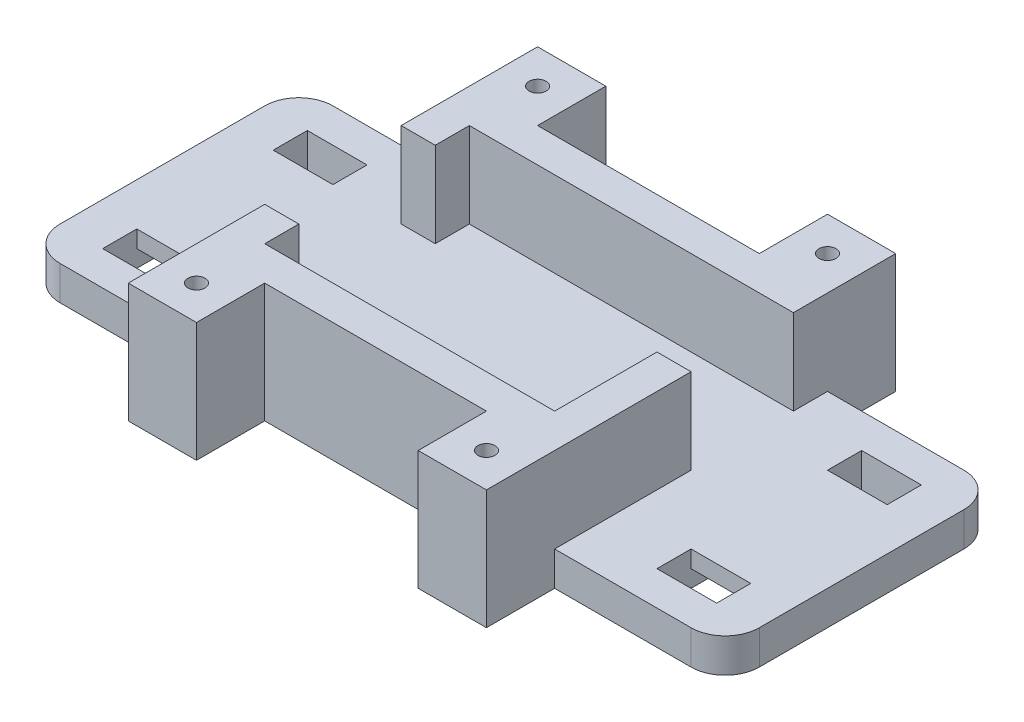
SolidWorks part; units mm, degrees
ref_plane "Front Plane" through (0, 0, 0) normal (0, 0, 1) x (1, 0, 0)
ref_plane "Top Plane" through (0, 0, 0) normal (0, 1, 0) x (1, 0, 0)
ref_plane "Right Plane" through (0, 0, 0) normal (1, 0, 0) x (0, 0, -1)
sketch "Sketch1" plane through (0, 0, 0) normal (0, 1, 0) x (1, 0, 0)
  line L0 (2, 14) -> (-19, 14)
  line L1 (0, 0) -> (-17, 0)
  line L2 (0, 0) -> (0, 12)
  line L3 (0, 12) -> (-17, 12)
  line L4 (-17, 0) -> (-17, 12)
  line L5 (-19, -2) -> (-19, 14)
  line L6 (2, -2) -> (-19, -2)
  line L7 (2, -2) -> (2, 14)
  dimension "D1" = 12
  dimension "D2" = 17
  dimension "D3" = 2
extrude "Boss-Extrude1" add sketch "Sketch1" along normal blind 2 contours L4 L1 L2 L3 | L6 L7 L0 L5 L1 L4 L3 L2 region at (1.736, 0, -6) region at (-8.5, 0, -6)
extrude "Boss-Extrude2" add sketch "Sketch1<6>" along normal offset from surface (7 mm away) 5 up to face at (-8.5, 2, -6) offset beyond the face yes
sketch "Sketch1<6>" plane through (0, 0, 0) normal (0, 1, 0) x (1, 0, 0) same geometry as "Sketch1"
sketch "Sketch2" plane through (0, 0, 0) normal (0, -1, 0) x (1, 0, 0)
  line L0 (-19, 2) -> (-19, -14) construction
  line L1 (-29, 2) -> (12, 2)
  line L2 (-29, 2) -> (-29, -14)
  line L3 (-29, -14) -> (12, -14)
  line L4 (12, 2) -> (12, -14)
  line L5 (2, 2) -> (2, -14) construction
  line L6 (-19, 2) -> (2, 2) construction
  line L7 (2, -14) -> (-19, -14) construction
  dimension "D1" = 10
  dimension "D2" = 10
extrude "Boss-Extrude3" add sketch "Sketch2" along normal blind 2
sketch "Sketch3" plane through (0, 0, 0) normal (0, 1, 0) x (1, 0, 0)
  line L0 (-19, -2) -> (-29, -2) construction
  line L1 (-26.5, 12) -> (-23, 12)
  line L2 (-26.5, 12) -> (-26.5, 10)
  line L3 (-26.5, 10) -> (-23, 10)
  line L4 (-23, 12) -> (-23, 10)
  line L5 (-26.5, 2) -> (-23, 2)
  line L6 (-26.5, 2) -> (-26.5, 0)
  line L7 (-26.5, 0) -> (-23, 0)
  line L8 (-23, 2) -> (-23, 0)
  line L9 (-29, 14) -> (-19, 14) construction
  line L10 (-19, -2) -> (-19, 14) construction
  line L11 (6, 12) -> (9.5, 12)
  line L12 (6, 12) -> (6, 10)
  line L13 (6, 10) -> (9.5, 10)
  line L14 (9.5, 12) -> (9.5, 10)
  line L15 (6, 2) -> (9.5, 2)
  line L16 (6, 2) -> (6, 0)
  line L17 (6, 0) -> (9.5, 0)
  line L18 (9.5, 2) -> (9.5, 0)
  line L19 (2, 14) -> (12, 14) construction
  line L20 (12, -2) -> (2, -2) construction
  line L21 (2, -2) -> (2, 14) construction
  dimension "D1" = 3.5
  dimension "D2" = 3.5
  dimension "D3" = 2
  dimension "D4" = 2
  dimension "D5" = 2
  dimension "D6" = 2
  dimension "D7" = 4
  dimension "D8" = 3.5
  dimension "D9" = 2
  dimension "D10" = 2
  dimension "D11" = 2
  dimension "D12" = 4
  dimension "D13" = 4
  dimension "D14" = 0
extrude "Cut-Extrude1" cut sketch "Sketch3" against normal through all
sketch "Sketch4" plane through (0, -2, 0) normal (0, -1, 0) x (1, 0, 0)
  line L1 (-23, -10) -> (-26.5, -10)
  line L2 (-23, -10) -> (-23, -2)
  line L3 (-23, -2) -> (-26.5, -2)
  line L4 (-26.5, -10) -> (-26.5, -2)
  point P6 (-22.6325, -2)
  point P7 (-26.5, -10)
extrude "Cut-Extrude2" cut sketch "Sketch4" against normal blind 1
sketch "Sketch5" plane through (0, 7, 0) normal (0, 1, 0) x (1, 0, 0)
  line L0 (-17, 0) -> (-17, 12) construction
  line L1 (-17, 10) -> (-19, 10)
  line L2 (-17, 10) -> (-17, 2)
  line L3 (-17, 2) -> (-19, 2)
  line L4 (-19, 10) -> (-19, 2)
  line L5 (-19, 14) -> (-19, -2) construction
  line L6 (-17, 0) -> (0, 0) construction
  line L7 (0, 12) -> (-17, 12) construction
  line L8 (2, -2) -> (2, 14) construction
  line L9 (0, 12) -> (2, 12)
  line L10 (0, 12) -> (0, 6)
  line L11 (0, 6) -> (2, 6)
  line L12 (2, 12) -> (2, 6)
  dimension "D1" = 2
  dimension "D2" = 2
  dimension "D3" = 6
extrude "Cut-Extrude3" cut sketch "Sketch5" against normal up to surface (7 mm away) up to face at (-24.75, 0, -1)
sketch "Sketch7" plane through (0, 2, 0) normal (0, 1, 0) x (1, 0, 0)
  line L1 (-17, 12) -> (0, 12)
  line L2 (-17, 12) -> (-17, 0)
  line L3 (-17, 0) -> (0, 0)
  line L4 (0, 12) -> (0, 0)
  line M1 (-17, 0) -> (0, 0)
  line M2 (0, 0) -> (0, 6)
  line M3 (0, 6) -> (0, 12)
  line M4 (0, 12) -> (-17, 12)
  line M5 (-17, 12) -> (-17, 10)
  line M6 (-17, 10) -> (-17, 2)
  line M7 (-17, 2) -> (-17, 0)
extrude "Cut-Extrude4" cut sketch "Sketch7" along direction (0, 1, 0) on the side against the normal blind 2 contours M7 M1 M2 M3 M4 M5 M6 region at (-8.5, 2, -6)
sketch "Sketch8" plane through (0, 7, 0) normal (0, 1, 0) x (1, 0, 0)
  line L6 (-19, 10) -> (-17, 10)
  line L7 (-17, 10) -> (-17, 12)
  line L8 (-17, 2) -> (-19, 2)
  line L9 (-19, 2) -> (-19, -2)
  line L10 (-19, -2) -> (2, -2)
  line L11 (2, -2) -> (2, 6)
  line L12 (2, 6) -> (0, 6)
  line L13 (0, 6) -> (0, 0)
  line L14 (0, 0) -> (-17, 0)
  line L15 (-17, 0) -> (-17, 2)
  line L16 (-17, 2) -> (-19, 2)
  line L17 (-19, 2) -> (-19, -2)
  line L18 (-19, -2) -> (2, -2)
  line L19 (2, -2) -> (2, 6)
  line L20 (2, 6) -> (0, 6)
  line L21 (0, 6) -> (0, 0)
  line L22 (0, 0) -> (-17, 0)
  line L23 (-17, 0) -> (-17, 2)
  line L24 (-17, 12) -> (2, 12)
  line L25 (2, 12) -> (2, 14)
  line L26 (2, 14) -> (-19, 14)
  line L27 (-19, 14) -> (-19, 10)
  line L28 (-19, 10) -> (-17, 10)
  line L29 (-17, 10) -> (-17, 12)
  line L30 (-17, 12) -> (2, 12)
  line L31 (2, 12) -> (2, 14)
  line L32 (2, 14) -> (-19, 14)
  line L33 (-19, 14) -> (-19, 10)
  dimension "D1" = 0
  dimension "D2" = 0
extrude "Cut-Extrude5" cut sketch "Sketch8" against normal blind 2
sketch "Sketch9" plane through (0, 5, 0) normal (0, 1, 0) x (1, 0, 0)
  line L1 (-19, 14) -> (-15, 14)
  line L2 (-19, 14) -> (-19, 18)
  line L3 (-19, 18) -> (-15, 18)
  line L4 (-15, 14) -> (-15, 18)
  line L5 (2, 14) -> (-2, 14)
  line L6 (2, 14) -> (2, 18)
  line L7 (2, 18) -> (-2, 18)
  line L8 (-2, 14) -> (-2, 18)
  line L9 (2, -2) -> (-2, -2)
  line L10 (2, -2) -> (2, -6)
  line L11 (2, -6) -> (-2, -6)
  line L12 (-2, -2) -> (-2, -6)
  line L13 (-19, -2) -> (-15, -2)
  line L14 (-19, -2) -> (-19, -6)
  line L15 (-19, -6) -> (-15, -6)
  line L16 (-15, -2) -> (-15, -6)
  dimension "D1" = 4
  dimension "D2" = 4
  dimension "D3" = 4
  dimension "D4" = 4
  dimension "D5" = 4
  dimension "D6" = 4
  dimension "D7" = 4
  dimension "D8" = 4
extrude "Boss-Extrude4" add sketch "Sketch9" along direction (0, -1, 0) on the side against the normal up to surface (7 mm away) up to face at (-24.75, -2, -6)
sketch "Sketch10" plane through (0, 5, 0) normal (0, 1, 0) x (1, 0, 0)
  line L0 (-19, 18) -> (-19, 10) construction
  line L1 (-15, 18) -> (-19, 18) construction
  line L2 (-2, 18) -> (-2, 14) construction
  line L3 (2, 18) -> (-2, 18) construction
  line L4 (2, -6) -> (2, 6) construction
  line L5 (-2, -6) -> (2, -6) construction
  line L6 (-15, -6) -> (-15, -2) construction
  line L7 (-19, -6) -> (-15, -6) construction
  circle A0 centre (-17, 16) radius 0.5
  circle A1 centre (0, 16) radius 0.5
  circle A2 centre (0, -4) radius 0.5
  circle A3 centre (-17, -4) radius 0.5
  point P16 (0.134, 16.7692)
  point P23 (0, 0)
  dimension "D9" = 1
  dimension "D10" = 1
  dimension "D11" = 1
  dimension "D12" = 1
  dimension "D1" = 2
  dimension "D2" = 2
  dimension "D3" = 2
  dimension "D4" = 2
  dimension "D5" = 2
  dimension "D6" = 2
  dimension "D7" = 2
  dimension "D8" = 2
extrude "Cut-Extrude6" cut sketch "Sketch10" against normal through all
sketch "Sketch11" plane through (0, -2, 0) normal (0, -1, 0) x (1, 0, 0)
  line L1 (6, -2) -> (9.5, -2)
  line L2 (6, -2) -> (6, -10)
  line L3 (6, -10) -> (9.5, -10)
  line L4 (9.5, -2) -> (9.5, -10)
extrude "Cut-Extrude7" cut sketch "Sketch11" against normal blind 1
fillet "Fillet1" radius 2 4 edges at (-29, -1, -14) (-29, -1, 2) (12, -1, 2) (12, -1, -14)
